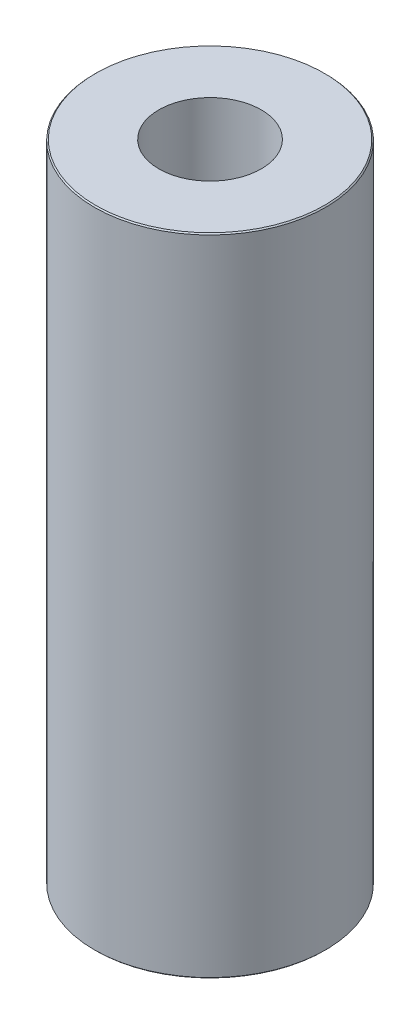
SolidWorks part; units mm, degrees
ref_plane "Front Plane" through (0, 0, 0) normal (0, 0, 1) x (1, 0, 0)
ref_plane "Top Plane" through (0, 0, 0) normal (0, 1, 0) x (1, 0, 0)
ref_plane "Right Plane" through (0, 0, 0) normal (1, 0, 0) x (0, 0, -1)
sketch "Sketch1" plane through (0, 0, 0) normal (0, 1, 0) x (1, 0, 0)
  circle A0 centre (0, 0) radius 47.5
  dimension "SHAFT_OD" = 95
extrude "Boss-Extrude1" add sketch "Sketch1" along normal blind 265.2903
sketch "Sketch2" plane through (0, 0, 0) normal (0, 1, 0) x (1, 0, 0)
  circle A0 centre (0, 0) radius 21.0498
  dimension "BORE_D" = 42.0995
extrude "Cut-Extrude1" cut sketch "Sketch2" along normal through all
chamfer "Chamfer1" distance 0.4782 angle 45 2 edges at (0, 265.2903, 47.5) (0, 0, 47.5)
